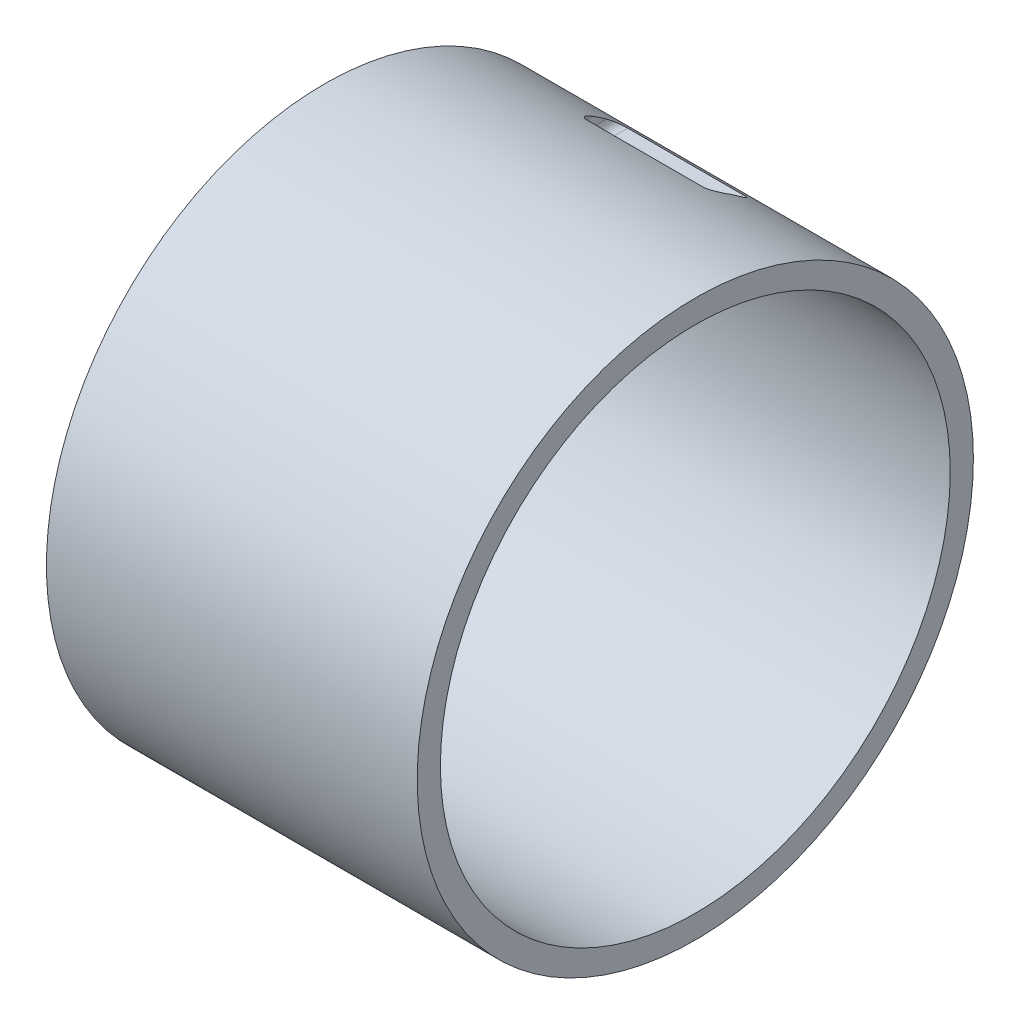
SolidWorks part; units mm, degrees
material "6061-T6 (SS)"
ref_plane "Front Plane" through (0, 0, 0) normal (0, 0, 1) x (1, 0, 0)
ref_plane "Top Plane" through (0, 0, 0) normal (0, 1, 0) x (1, 0, 0)
ref_plane "Right Plane" through (0, 0, 0) normal (1, 0, 0) x (0, 0, -1)
sketch "Sketch1" plane through (0, 0, 0) normal (1, 0, 0) x (0, 0, -1)
  circle A0 centre (0, 0) radius 69.85
  circle A1 centre (0, 0) radius 76.2
  dimension "D1" = 6.35
  dimension "D2" = 139.7
extrude "Boss-Extrude1" add sketch "Sketch1" along normal mid plane 101.6
ref_plane "Plane1" through (31.75, 0, 0) normal (1, 0, 0) x (0, 0, -1)
ref_plane "Plane2" through (-31.75, 0, 0) normal (-1, 0, 0) x (0, 0, 1)
ref_axis "Axis1" through (50.8, 0, 0) along (-1, 0, 0)
sketch "Sketch4" plane through (0, 0, 0) normal (0, 0, 1) x (1, 0, 0)
  line L0 (0, -76.2) -> (0, 76.2) construction
  line L1 (-18.415, 66.675) -> (18.415, 66.675)
  line L2 (-18.415, 66.675) -> (-18.415, 59.055)
  line L3 (-18.415, 59.055) -> (18.415, 59.055)
  line L4 (18.415, 66.675) -> (18.415, 59.055)
  line L9 (50.8, 76.2) -> (-50.8, 76.2) construction
  point P4 (0, 59.055)
  dimension "D1" = 36.83
  dimension "D3" = 7.62
  dimension "D4" = 9.525
extrude "Cut-Extrude1" cut sketch "Sketch4" against normal up to surface (36.8902 mm away) up to face at (50.8, 0, -76.2)
fillet "Fillet1" radius 2.54 4 edges at (-18.415, 59.055, -42.7293) (-18.415, 66.675, -28.855) (18.415, 66.675, -28.855) (18.415, 59.055, -42.7293)
